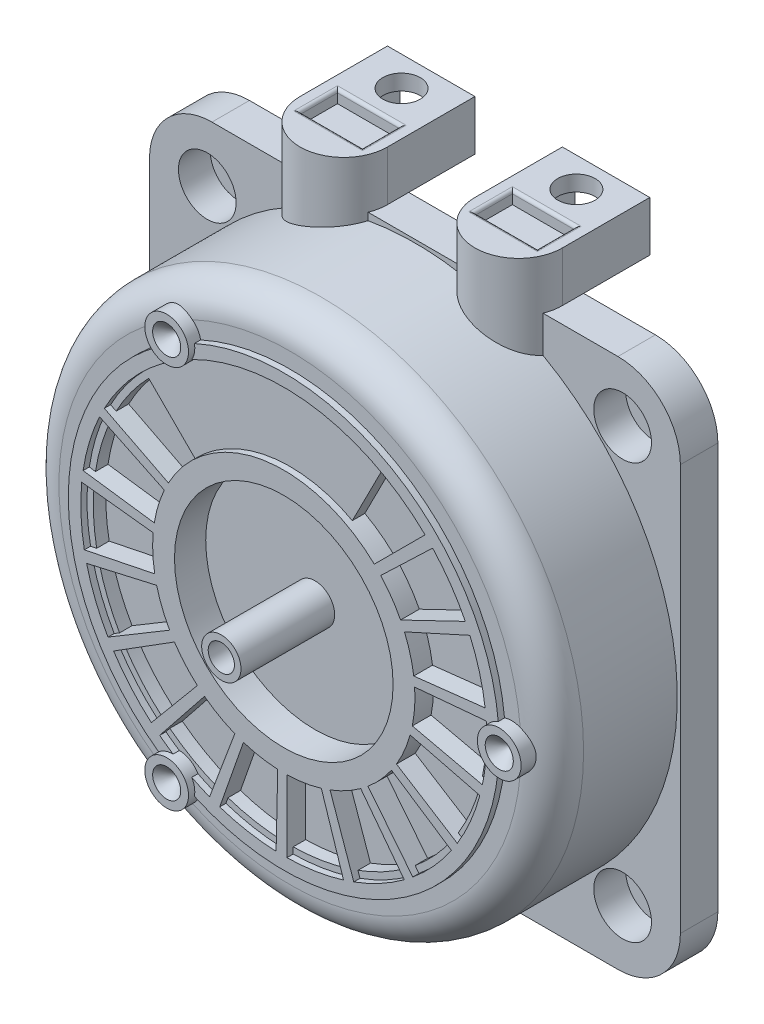
SolidWorks part; units mm, degrees
ref_plane "Спереди" through (0, 0, 0) normal (0, 0, 1) x (1, 0, 0)
ref_plane "Сверху" through (0, 0, 0) normal (0, 1, 0) x (1, 0, 0)
ref_plane "Справа" through (0, 0, 0) normal (1, 0, 0) x (0, 0, -1)
sketch "Эскиз1" plane through (0, 0, 0) normal (0, 0, 1) x (1, 0, 0)
  line L1 (0, 0) -> (85, 0)
  line L2 (0, 0) -> (0, 85)
  line L3 (0, 85) -> (85, 85)
  line L4 (85, 0) -> (85, 85)
  dimension "D1" = 85
  dimension "D2" = 85
extrude "Бобышка-Вытянуть1" add sketch "Эскиз1" along normal blind 6
fillet "Скругление1" radius 10 4 edges at (85, 0, 3) (0, 0, 3) (0, 85, 3) (85, 85, 3)
sketch "Эскиз2" plane through (0, 0, 6) normal (0, 0, 1) x (1, 0, 0)
  circle A0 centre (42.5, 42.5) radius 42
extrude "Бобышка-Вытянуть2" add sketch "Эскиз2" along normal blind 20
fillet "Скругление2" radius 5 1 edges at (84.5, 42.5, 26)
sketch "Эскиз3" plane through (0, 0, 26) normal (0, 0, 1) x (1, 0, 0)
  line L0 (61.198, 52.0595) -> (70.66, 56.6161)
  line L1 (58.0199, 56.6468) -> (65.6107, 63.9043)
  line L2 (56.9915, 57.6986) -> (64.4175, 65.1246)
  line L3 (63.3061, 45.3474) -> (73.742, 46.5233)
  line L4 (61.8214, 50.727) -> (71.3832, 55.0702)
  line L5 (63.0789, 38.3158) -> (73.3176, 35.9789)
  line L6 (63.4544, 43.8839) -> (73.9141, 44.8253)
  line L7 (60.5422, 31.7539) -> (69.4345, 26.1665)
  line L8 (62.7355, 36.8855) -> (72.9192, 34.3194)
  line L9 (55.9805, 26.3979) -> (62.5284, 18.1872)
  line L10 (59.7456, 30.5172) -> (68.5103, 24.7316)
  line L11 (49.9058, 22.8492) -> (53.3744, 12.9366)
  line L12 (54.8202, 25.4937) -> (61.1822, 17.1381)
  line L13 (43, 21.506) -> (43, 11.004)
  line L14 (48.512, 22.379) -> (51.7573, 12.391)
  line L15 (36.038, 22.5189) -> (32.5695, 12.6063)
  line L16 (41.5291, 21.5225) -> (41.2934, 11.0231)
  line L17 (29.8013, 25.7744) -> (23.2535, 17.5637)
  line L18 (34.6551, 23.0203) -> (30.965, 13.188)
  line L19 (24.9898, 30.9071) -> (16.0976, 25.3197)
  line L20 (28.6616, 26.7045) -> (21.9311, 18.6427)
  line L21 (22.1436, 37.3409) -> (11.9049, 35.004)
  line L22 (24.2212, 32.1614) -> (15.2058, 26.7749)
  line L23 (21.582, 44.3537) -> (11.146, 45.5296)
  line L24 (52.4766, 60.9788) -> (57.2444, 70.3362)
  line L25 (21.8324, 38.7787) -> (11.5438, 36.6721)
  line L26 (23.3681, 51.1585) -> (13.9061, 55.7151)
  line L27 (21.7631, 45.8136) -> (11.3561, 47.2233)
  line L28 (27.3014, 56.9915) -> (19.8754, 64.4175)
  line L29 (24.0212, 52.4766) -> (14.6638, 57.2444)
  arc A4 (64.4175, 65.1246) -> (57.2444, 70.3362) centre (42.5, 42.5) ccw
  arc A6 (56.9915, 57.6986) -> (52.4766, 60.9788) centre (42.5, 42.5) ccw
  arc A7 (70.66, 56.6161) -> (65.6107, 63.9043) centre (42.5, 42.5) ccw
  arc A8 (61.198, 52.0595) -> (58.0199, 56.6468) centre (42.5, 42.5) ccw
  arc A9 (73.742, 46.5233) -> (71.3832, 55.0702) centre (42.5, 42.5) ccw
  arc A10 (63.3061, 45.3474) -> (61.8214, 50.727) centre (42.5, 42.5) ccw
  arc A11 (73.3176, 35.9789) -> (73.9141, 44.8253) centre (42.5, 42.5) ccw
  arc A12 (63.0789, 38.3158) -> (63.4544, 43.8839) centre (42.5, 42.5) ccw
  arc A13 (69.4345, 26.1665) -> (72.9192, 34.3194) centre (42.5, 42.5) ccw
  arc A14 (60.5422, 31.7539) -> (62.7355, 36.8855) centre (42.5, 42.5) ccw
  arc A15 (62.5284, 18.1872) -> (68.5103, 24.7316) centre (42.5, 42.5) ccw
  arc A16 (55.9805, 26.3979) -> (59.7456, 30.5172) centre (42.5, 42.5) ccw
  arc A17 (53.3744, 12.9366) -> (61.1822, 17.1381) centre (42.5, 42.5) ccw
  arc A18 (49.9058, 22.8492) -> (54.8202, 25.4937) centre (42.5, 42.5) ccw
  arc A19 (43, 11.004) -> (51.7573, 12.391) centre (42.5, 42.5) ccw
  arc A20 (43, 21.506) -> (48.512, 22.379) centre (42.5, 42.5) ccw
  arc A21 (32.5695, 12.6063) -> (41.2934, 11.0231) centre (42.5, 42.5) ccw
  arc A22 (36.038, 22.5189) -> (41.5291, 21.5225) centre (42.5, 42.5) ccw
  arc A23 (23.2535, 17.5637) -> (30.965, 13.188) centre (42.5, 42.5) ccw
  arc A24 (29.8013, 25.7744) -> (34.6551, 23.0203) centre (42.5, 42.5) ccw
  arc A25 (16.0976, 25.3197) -> (21.9311, 18.6427) centre (42.5, 42.5) ccw
  arc A26 (24.9898, 30.9071) -> (28.6616, 26.7045) centre (42.5, 42.5) ccw
  arc A27 (11.9049, 35.004) -> (15.2058, 26.7749) centre (42.5, 42.5) ccw
  arc A28 (22.1436, 37.3409) -> (24.2212, 32.1614) centre (42.5, 42.5) ccw
  arc A29 (11.146, 45.5296) -> (11.5438, 36.6721) centre (42.5, 42.5) ccw
  arc A30 (21.582, 44.3537) -> (21.8324, 38.7787) centre (42.5, 42.5) ccw
  arc A31 (13.9061, 55.7151) -> (11.3561, 47.2233) centre (42.5, 42.5) ccw
  arc A32 (23.3681, 51.1585) -> (21.7631, 45.8136) centre (42.5, 42.5) ccw
  arc A33 (19.8754, 64.4175) -> (14.6638, 57.2444) centre (42.5, 42.5) ccw
  arc A34 (27.3014, 56.9915) -> (24.0212, 52.4766) centre (42.5, 42.5) ccw
  point P65 (42.5, 42.5)
  dimension "D1" = 15
extrude "Вырез-Вытянуть1" cut sketch "Эскиз3" against normal blind 2
sketch "Эскиз4" plane through (0, 0, 26) normal (0, 0, 1) x (1, 0, 0)
  line L0 (56.9915, 57.6986) -> (64.4175, 65.1246) construction
  line L2 (27.3014, 56.9915) -> (19.8754, 64.4175)
  line L3 (14.6638, 57.2444) -> (24.0212, 52.4766)
  line L5 (13.7727, 57.6984) -> (24.0212, 52.4766)
  line L6 (23.3681, 51.1585) -> (13.9061, 55.7151)
  line L7 (11.3561, 47.2233) -> (21.7631, 45.8136)
  line L8 (23.3681, 51.1585) -> (13.005, 56.1491)
  line L9 (10.3651, 47.3575) -> (21.7631, 45.8136)
  line L10 (61.198, 52.0595) -> (70.66, 56.6161) construction
  line L11 (65.6107, 63.9043) -> (58.0199, 56.6468) construction
  line L12 (60.5422, 31.7539) -> (69.4345, 26.1665) construction
  line L13 (72.9192, 34.3194) -> (62.7355, 36.8855) construction
  line L14 (63.3061, 45.3474) -> (73.742, 46.5233) construction
  line L15 (71.3832, 55.0702) -> (61.8214, 50.727) construction
  line L16 (63.0789, 38.3158) -> (73.3176, 35.9789) construction
  line L17 (73.9141, 44.8253) -> (63.4544, 43.8839) construction
  line L18 (55.9805, 26.3979) -> (62.5284, 18.1872) construction
  line L19 (68.5103, 24.7316) -> (59.7456, 30.5172) construction
  line L20 (43, 21.506) -> (43, 11.004) construction
  line L21 (51.7573, 12.391) -> (48.512, 22.379) construction
  line L22 (49.9058, 22.8492) -> (53.3744, 12.9366) construction
  line L23 (61.1822, 17.1381) -> (54.8202, 25.4937) construction
  line L24 (36.038, 22.5189) -> (32.5695, 12.6063) construction
  line L25 (41.2934, 11.0231) -> (41.5291, 21.5225) construction
  line L26 (29.8013, 25.7744) -> (23.2535, 17.5637) construction
  line L27 (30.965, 13.188) -> (34.6551, 23.0203) construction
  line L28 (24.9898, 30.9071) -> (16.0976, 25.3197) construction
  line L29 (21.9311, 18.6427) -> (28.6616, 26.7045) construction
  line L30 (22.1436, 37.3409) -> (11.9049, 35.004) construction
  line L31 (15.2058, 26.7749) -> (24.2212, 32.1614) construction
  line L32 (21.582, 44.3537) -> (11.146, 45.5296) construction
  line L33 (11.5438, 36.6721) -> (21.8324, 38.7787) construction
  line L34 (56.9915, 57.6986) -> (65.1247, 65.8318)
  line L36 (61.198, 52.0595) -> (71.5611, 57.05)
  line L37 (66.3336, 64.5955) -> (58.0199, 56.6468)
  line L38 (60.5422, 31.7539) -> (70.2813, 25.6344)
  line L39 (73.889, 34.075) -> (62.7355, 36.8855)
  line L40 (63.3061, 45.3474) -> (74.7358, 46.6353)
  line L41 (72.2938, 55.4838) -> (61.8214, 50.727)
  line L42 (63.0789, 38.3158) -> (74.2927, 35.7564)
  line L43 (74.9102, 44.9149) -> (63.4544, 43.8839)
  line L44 (55.9805, 26.3979) -> (63.1519, 17.4052)
  line L45 (69.345, 24.1807) -> (59.7456, 30.5172)
  line L46 (43, 21.506) -> (43, 10.0038)
  line L47 (52.0663, 11.4398) -> (48.512, 22.379)
  line L48 (49.9058, 22.8492) -> (53.7047, 11.9926)
  line L49 (61.788, 16.3424) -> (54.8202, 25.4937)
  line L50 (36.038, 22.5189) -> (32.2391, 11.6623)
  line L51 (41.271, 10.0232) -> (41.5291, 21.5225)
  line L52 (29.8013, 25.7744) -> (22.6299, 16.7817)
  line L53 (30.6136, 12.2517) -> (34.6551, 23.0203)
  line L54 (24.9898, 30.9071) -> (15.2507, 24.7876)
  line L55 (21.2902, 17.8749) -> (28.6616, 26.7045)
  line L56 (22.1436, 37.3409) -> (10.9299, 34.7815)
  line L57 (14.3473, 26.262) -> (24.2212, 32.1614)
  line L58 (21.582, 44.3537) -> (10.1522, 45.6416)
  line L59 (10.564, 36.4715) -> (21.8324, 38.7787)
  arc A3 (27.3014, 56.9915) -> (24.0212, 52.4766) centre (42.5, 42.5) ccw
  arc A4 (19.8754, 64.4175) -> (14.6638, 57.2444) centre (42.5, 42.5) ccw
  arc A7 (23.3681, 51.1585) -> (21.7631, 45.8136) centre (42.5, 42.5) ccw
  arc A8 (13.9061, 55.7151) -> (11.3561, 47.2233) centre (42.5, 42.5) ccw
  arc A34 (23.3681, 51.1585) -> (21.7631, 45.8136) centre (42.5, 42.5) ccw
  arc A60 (21.582, 44.3537) -> (21.8324, 38.7787) centre (42.5, 42.5) ccw
  arc A74 (22.1436, 37.3409) -> (24.2212, 32.1614) centre (42.5, 42.5) ccw
  arc A75 (24.9898, 30.9071) -> (28.6616, 26.7045) centre (42.5, 42.5) ccw
  arc A76 (29.8013, 25.7744) -> (34.6551, 23.0203) centre (42.5, 42.5) ccw
  arc A77 (36.038, 22.5189) -> (41.5291, 21.5225) centre (42.5, 42.5) ccw
  arc A78 (43, 21.506) -> (48.512, 22.379) centre (42.5, 42.5) ccw
  arc A79 (49.9058, 22.8492) -> (54.8202, 25.4937) centre (42.5, 42.5) ccw
  arc A80 (55.9805, 26.3979) -> (59.7456, 30.5172) centre (42.5, 42.5) ccw
  arc A81 (60.5422, 31.7539) -> (62.7355, 36.8855) centre (42.5, 42.5) ccw
  arc A82 (63.0789, 38.3158) -> (63.4544, 43.8839) centre (42.5, 42.5) ccw
  arc A83 (63.3061, 45.3474) -> (61.8214, 50.727) centre (42.5, 42.5) ccw
  arc A84 (61.198, 52.0595) -> (58.0199, 56.6468) centre (42.5, 42.5) ccw
  arc A85 (56.9915, 57.6986) -> (24.0212, 52.4766) centre (42.5, 42.5) ccw
  circle A86 centre (42.5, 42.5) radius 34.5
  arc A87 (13.005, 56.1491) -> (10.3651, 47.3575) centre (42.5, 42.5) ccw
  arc A88 (10.1522, 45.6416) -> (10.564, 36.4715) centre (42.5, 42.5) ccw
  arc A89 (10.9299, 34.7815) -> (14.3473, 26.262) centre (42.5, 42.5) ccw
  arc A90 (15.2507, 24.7876) -> (21.2902, 17.8749) centre (42.5, 42.5) ccw
  arc A91 (22.6299, 16.7817) -> (30.6136, 12.2517) centre (42.5, 42.5) ccw
  arc A92 (32.2391, 11.6623) -> (41.271, 10.0232) centre (42.5, 42.5) ccw
  arc A93 (43, 10.0038) -> (52.0663, 11.4398) centre (42.5, 42.5) ccw
  arc A94 (53.7047, 11.9926) -> (61.788, 16.3424) centre (42.5, 42.5) ccw
  arc A95 (63.1519, 17.4052) -> (69.345, 24.1807) centre (42.5, 42.5) ccw
  arc A96 (70.2813, 25.6344) -> (73.889, 34.075) centre (42.5, 42.5) ccw
  arc A97 (74.2927, 35.7564) -> (74.9102, 44.9149) centre (42.5, 42.5) ccw
  arc A98 (74.7358, 46.6353) -> (72.2938, 55.4838) centre (42.5, 42.5) ccw
  arc A99 (71.5611, 57.05) -> (66.3336, 64.5955) centre (42.5, 42.5) ccw
  arc A100 (65.1247, 65.8318) -> (13.7727, 57.6984) centre (42.5, 42.5) ccw
  dimension "D2" = 0
  dimension "D3" = 0
extrude "Бобышка-Вытянуть3" add sketch "Эскиз4" along normal blind 1
sketch "Эскиз5" plane through (0, 0, 27) normal (0, 0, 1) x (1, 0, 0)
  circle A0 centre (42.5, 42.5) radius 17.5
  dimension "D1" = 35
extrude "Вырез-Вытянуть3" cut sketch "Эскиз5" against normal blind 5
sketch "Эскиз7" plane through (0, 0, 26) normal (0, 0, 1) x (1, 0, 0)
  circle A3 centre (24.75, 73.2439) radius 3.5
  circle A5 centre (78, 42.5) radius 3.5
  circle A6 centre (24.75, 11.7561) radius 3.5
  dimension "D3" = 7
  dimension "D4" = 7
  dimension "D5" = 7
extrude "Бобышка-Вытянуть5" add sketch "Эскиз7" along normal blind 2 and the other way blind 15
sketch "Эскиз8" plane through (0, 0, 28) normal (0, 0, 1) x (1, 0, 0)
  circle A0 centre (24.75, 11.7561) radius 2.25
  circle A2 centre (78, 42.5) radius 2.25
  circle A3 centre (24.75, 73.2439) radius 2.25
extrude "Вырез-Вытянуть4" cut sketch "Эскиз8" against normal blind 2
chamfer "Фаска1" distance 2 angle 45 3 edges at (27, 11.7561, 26) (80.25, 42.5, 26) (27, 73.2439, 26)
sketch "Эскиз9" plane through (0, 0, 22) normal (0, 0, 1) x (1, 0, 0)
  circle A0 centre (42.5, 42.5) radius 3.15
  dimension "D1" = 6.3
sketch "Эскиз11" plane through (0, 85, 0) normal (0, 1, 0) x (1, 0, 0)
  line L6 (63.5, -3.4) -> (63.5, 10.6)
  line L7 (63.5, 10.6) -> (49.5, 10.6)
  line L8 (49.5, -3.4) -> (49.5, 10.6)
  line L9 (35.5, -3.4) -> (35.5, 10.6)
  line L10 (21.5, -3.4) -> (21.5, 10.6)
  line L11 (21.5, 10.6) -> (35.5, 10.6)
  arc A2 (49.5, -3.4) -> (63.5, -3.4) centre (56.5, -3.4) ccw
  arc A3 (21.5, -3.4) -> (35.5, -3.4) centre (28.5, -3.4) ccw
extrude "Бобышка-Вытянуть6" add sketch "Эскиз11" along normal blind 8
sketch "Эскиз12" plane through (0, 85, 0) normal (0, -1, 0) x (1, 0, 0)
  line L0 (21.5, 3.4) -> (35.5, 3.4)
  line L1 (49.5, 3.4) -> (63.5, 3.4)
  arc A0 (63.5, 3.4) -> (49.5, 3.4) centre (56.5, 3.4) ccw construction
  arc A1 (63.5, 3.4) -> (49.5, 3.4) centre (56.5, 3.4) ccw
  arc A2 (35.5, 3.4) -> (21.5, 3.4) centre (28.5, 3.4) ccw construction
  arc A3 (35.5, 3.4) -> (21.5, 3.4) centre (28.5, 3.4) ccw
extrude "Бобышка-Вытянуть7" add sketch "Эскиз12" along normal up to surface (1.0874 mm away) up to face at (84.5, 42.5, 21)
sketch "Эскиз13" plane through (0, 0, -10.6) normal (0, 0, -1) x (-1, 0, 0)
  line L1 (-63.5, 85) -> (-49.5, 85) construction
  line L2 (-61.5, 85) -> (-61.5, 90.5)
  line L3 (-61.5, 90.5) -> (-51.5, 90.5)
  line L4 (-51.5, 90.5) -> (-51.5, 85)
  line L5 (-51.5, 85) -> (-61.5, 85)
  line L6 (-35.5, 85) -> (-21.5, 85) construction
  line L7 (-33.5, 85) -> (-33.5, 90.5)
  line L8 (-33.5, 90.5) -> (-23.5, 90.5)
  line L9 (-23.5, 90.5) -> (-23.5, 85)
  line L10 (-35.5, 85) -> (-21.5, 85) construction
  line L11 (-23.5, 85) -> (-33.5, 85)
extrude "Вырез-Вытянуть6" cut sketch "Эскиз13" against normal blind 14
sketch "Эскиз14" plane through (0, 93, 0) normal (0, 1, 0) x (1, 0, 0)
  line L0 (42.5, 3.4982) -> (42.5, -10.625) construction
  line L1 (61.5, -5.4) -> (61.5, 0.6)
  line L2 (23.5, 0.6) -> (33.5, 0.6)
  line L9 (33.5, 0.6) -> (33.5, -5.4)
  line L10 (33.5, -5.4) -> (23.5, -5.4)
  line L11 (23.5, -5.4) -> (23.5, 0.6)
  line L13 (51.5, -5.4) -> (61.5, -5.4)
  line L14 (51.5, 0.6) -> (51.5, -5.4)
  line L15 (61.5, 0.6) -> (51.5, 0.6)
extrude "Вырез-Вытянуть7" cut sketch "Эскиз14" against normal blind 2
fillet "Скругление3" radius 0.5 8 edges at (61.5, 93, 2.4) (56.5, 93, -0.6) (51.5, 93, 2.4) (56.5, 93, 5.4) (33.5, 93, 2.4) (28.5, 93, 5.4) (23.5, 93, 2.4) (28.5, 93, -0.6)
sketch "Эскиз15" plane through (0, 93, 0) normal (0, 1, 0) x (1, 0, 0)
  circle A0 centre (28.5, 5.85) radius 3
  circle A1 centre (56.5, 5.85) radius 3
  dimension "D1" = 6
  dimension "D2" = 6
extrude "Вырез-Вытянуть8" cut sketch "Эскиз15" against normal blind 11
hole_wizard "Отверстие обработанное метчиком M51" positions "Эскиз16" profile "Эскиз17" tap size "M5" standard "ISO"
sketch "Эскиз16" plane through (0, 0, 6) normal (0, 0, 1) x (1, 0, 0)
  point P0 (9.25, 9.25)
  point P2 (9.25, 75.75)
  point P4 (75.75, 75.75)
  point P6 (75.75, 9.25)
sketch "Эскиз17" plane through (9.25, 9.25, 6) normal (1, 0, 0) x (0, -1, 0)
  line L0 (0, 0) -> (0, 39.7618)
  line L1 (0, 39.7618) -> (2.1, 38.5)
  line L2 (2.1, 38.5) -> (2.1, 0)
  line L5 (2.1, 0) -> (0, 0)
  line L10 (0, 39.7618) -> (-2.1, 38.5) construction
  line L11 (0, -6.35) -> (0, 107.95) construction
  dimension "Диаметр сверла" = 4.2
  dimension "Глубина сверла" = 38.5
  dimension "Угол заточки сверла" = 118
cosmetic thread "Отверстие резьбы1" parameters "D1"=7, "D2"=5
cosmetic thread "Отверстие резьбы2" parameters "D1"=7, "D2"=5
cosmetic thread "Отверстие резьбы3" parameters "D1"=7, "D2"=5
cosmetic thread "Отверстие резьбы4" parameters "D1"=7, "D2"=5
extrude "Бобышка-Вытянуть8" add sketch "Эскиз9" along normal blind 15
hole_wizard "Отверстие обработанное метчиком M52" positions "Эскиз20" profile "Эскиз21" tap size "M5" standard "ISO"
sketch "Эскиз20" plane through (0, 0, 37) normal (0, 0, 1) x (1, 0, 0)
  point P0 (42.5, 42.5)
sketch "Эскиз21" plane through (42.5, 42.5, 37) normal (1, 0, 0) x (0, -1, 0)
  line L0 (0, 0) -> (0, 15.2618)
  line L1 (0, 15.2618) -> (2.1, 14)
  line L2 (2.1, 14) -> (2.1, 0)
  line L5 (2.1, 0) -> (0, 0)
  line L10 (0, 15.2618) -> (-2.1, 14) construction
  line L11 (0, -6.35) -> (0, 107.95) construction
  dimension "Диаметр сверла" = 4.2
  dimension "Глубина сверла" = 14
  dimension "Угол заточки сверла" = 118
cosmetic thread "Отверстие резьбы8" parameters "D1"=10, "D2"=5
sketch "Эскиз22" plane through (0, 0, 6) normal (0, 0, 1) x (1, 0, 0)
  circle A0 centre (75.75, 75.75) radius 4.6188
  circle A1 centre (9.25, 75.75) radius 4.62
  circle A2 centre (9.25, 9.25) radius 4.62
  circle A3 centre (75.75, 9.25) radius 4.62
extrude "Вырез-Вытянуть9" cut sketch "Эскиз22" against normal blind 5.1
